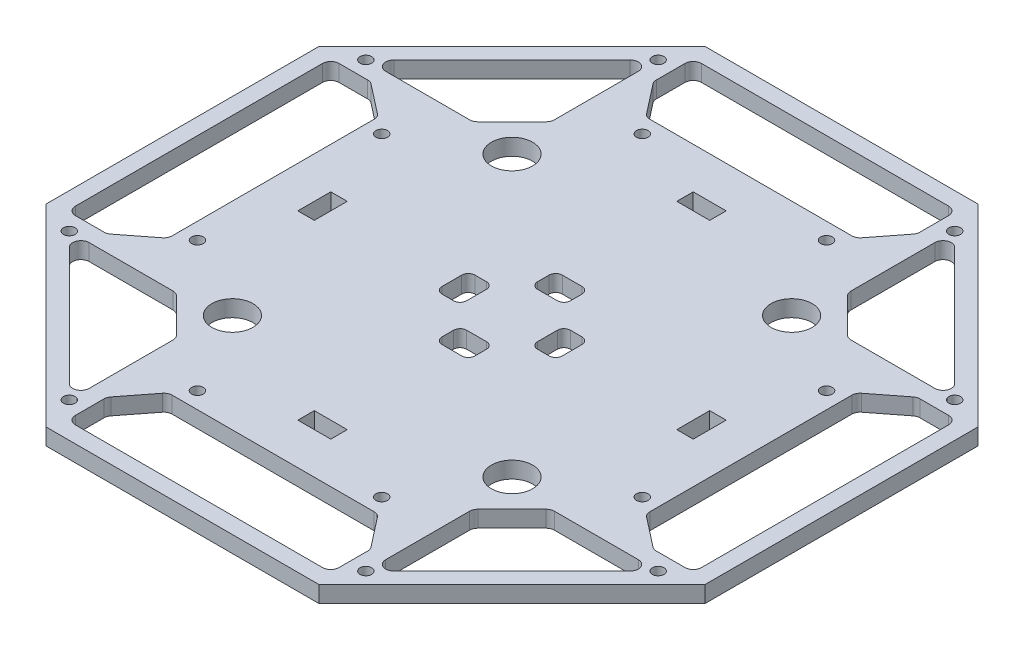
SolidWorks part; units mm, degrees
material "Custom Plastic"
ref_plane "Front Plane" through (0, 0, 0) normal (0, 0, 1) x (1, 0, 0)
ref_plane "Top Plane" through (0, 0, 0) normal (0, 1, 0) x (1, 0, 0)
ref_plane "Right Plane" through (0, 0, 0) normal (1, 0, 0) x (0, 0, -1)
ref_axis "Axis1" through (0, -0.2997, 0) along (0, 1, 0)
sketch "Base sketch" plane through (0, 0, 0) normal (0, 1, 0) x (1, 0, 0)
  line L1 (-127, 52.6051) -> (-127, -52.6051)
  line L2 (-127, -52.6051) -> (-52.6051, -127)
  line L3 (-52.6051, -127) -> (52.6051, -127)
  line L4 (52.6051, -127) -> (127, -52.6051)
  line L5 (127, -52.6051) -> (127, 52.6051)
  line L6 (127, 52.6051) -> (52.6051, 127)
  line L7 (52.6051, 127) -> (-52.6051, 127)
  line L8 (-52.6051, 127) -> (-127, 52.6051)
  circle A0 centre (0, 0) radius 127 construction
  dimension "D1" = 254
extrude "Base" add sketch "Base sketch" along normal blind 6.35
sketch "Sketch4" plane through (0, 6.35, 0) normal (0, 1, 0) x (1, 0, 0)
  line L0 (0, 0) -> (0, 127) construction
  line L1 (52.6051, 127) -> (-52.6051, 127) construction
  line L4 (-6.35, 69.85) -> (6.35, 69.85)
  line L5 (-6.35, 69.85) -> (-6.35, 76.2)
  line L6 (-6.35, 76.2) -> (6.35, 76.2)
  line L7 (6.35, 69.85) -> (6.35, 76.2)
  line L8 (-6.35, 69.85) -> (6.35, 76.2) construction
  line L10 (-6.35, 76.2) -> (6.35, 69.85) construction
  point P5 (0, 73.025)
  dimension "D1" = 6.35
  dimension "D2" = 12.7
  dimension "D3" = 53.975
extrude "Support cutouts" cut sketch "Sketch4" against normal up to next
pattern_circular "Support cutout pattern" count 4 over 360 about axis through (0, -0.2997, 0) along (0, 1, 0) of "Support cutouts"
sketch "Sketch11" plane through (0, 6.35, 0) normal (0, 1, 0) x (1, 0, 0)
  line L1 (98.425, 40.769) -> (40.769, 98.425) construction
  line L2 (40.769, 98.425) -> (-40.769, 98.425) construction
  line L3 (-40.769, 98.425) -> (-98.425, 40.769) construction
  line L4 (-98.425, 40.769) -> (-98.425, -40.769) construction
  line L5 (-98.425, -40.769) -> (-40.769, -98.425) construction
  line L6 (-40.769, -98.425) -> (40.769, -98.425) construction
  line L7 (40.769, -98.425) -> (98.425, -40.769) construction
  line L8 (98.425, -40.769) -> (98.425, 40.769) construction
  line L9 (-35.5085, 85.725) -> (-85.725, 35.5085)
  line L10 (-85.725, 35.5085) -> (-85.725, -35.5085)
  line L11 (-85.725, -35.5085) -> (-35.5085, -85.725)
  line L12 (-35.5085, -85.725) -> (35.5085, -85.725)
  line L13 (35.5085, -85.725) -> (85.725, -35.5085)
  line L14 (85.725, -35.5085) -> (85.725, 35.5085)
  line L15 (85.725, 35.5085) -> (35.5085, 85.725)
  line L16 (35.5085, 85.725) -> (-35.5085, 85.725)
  circle A0 centre (0, 0) radius 98.425 construction
  circle A1 centre (0, 0) radius 85.725 construction
  dimension "D1" = 196.85
  dimension "D2" = 12.7
hole_wizard "#8 Clearance Hole1" positions "Sketch13" profile "Sketch12" hole size "#8" standard "ANSI Inch" end condition through all
sketch "Sketch13" plane through (0, 6.35, 0) normal (0, 1, 0) x (1, 0, 0)
  point P0 (-85.725, 35.5085)
  point P3 (-35.5085, 85.725)
  point P6 (35.5085, 85.725)
  point P9 (85.725, 35.5085)
  point P12 (85.725, -35.5085)
  point P15 (35.5085, -85.725)
  point P18 (-35.5085, -85.725)
  point P21 (-85.725, -35.5085)
sketch "Sketch12" plane through (-85.725, 6.35, -35.5085) normal (1, 0, 0) x (0, 0, 1)
  line L0 (0, 0) -> (0, 6.35)
  line L1 (0, 6.35) -> (2.2479, 6.35)
  line L2 (2.2479, 6.35) -> (2.2479, 0)
  line L5 (2.2479, 0) -> (0, 0)
  line L11 (0, -6.35) -> (0, 107.95) construction
  dimension "Thru Hole Dia." = 4.4958
  dimension "Thru Hole Depth" = 6.35
sketch "Sketch14" plane through (0, 6.35, 0) normal (0, 1, 0) x (1, 0, 0)
  circle A0 centre (-53.8815, 53.8815) radius 7.9375
  circle A1 centre (53.8815, 53.8815) radius 7.9375
  circle A2 centre (53.8815, -53.8815) radius 7.9375
  circle A3 centre (-53.8815, -53.8815) radius 7.9375
  point P13 (0, 0)
  dimension "D2" = 15.875
  dimension "D1" = 76.2
  dimension "D3" = 4
extrude "Cable holes" cut sketch "Sketch14" against normal up to next
sketch "Sketch28" plane through (0, 6.35, 0) normal (0, 1, 0) x (1, 0, 0)
  line L0 (52.6051, 127) -> (-52.6051, 127) construction
  line L1 (57.15, 73.4808) -> (57.15, 105.8097)
  line L2 (62.5701, 108.0548) -> (108.0548, 62.5701)
  line L3 (71.2358, 58.0799) -> (58.0799, 71.2358)
  line L4 (-127, 52.6051) -> (-127, -52.6051) construction
  line L5 (105.8097, 57.15) -> (73.4808, 57.15)
  line L6 (73.4808, -57.15) -> (105.8097, -57.15)
  line L7 (108.0548, -62.5701) -> (62.5701, -108.0548)
  line L8 (58.0799, -71.2358) -> (71.2358, -58.0799)
  line L9 (57.15, -105.8097) -> (57.15, -73.4808)
  line L10 (-57.15, -73.4808) -> (-57.15, -105.8097)
  line L11 (-62.5701, -108.0548) -> (-108.0548, -62.5701)
  line L12 (-58.0799, 71.2358) -> (-71.2358, 58.0799)
  line L13 (-57.15, 105.8097) -> (-57.15, 73.4808)
  line L14 (-108.0548, 62.5701) -> (-62.5701, 108.0548)
  line L15 (-73.4808, 57.15) -> (-105.8097, 57.15)
  line L16 (-71.2358, -58.0799) -> (-58.0799, -71.2358)
  line L17 (-105.8097, -57.15) -> (-73.4808, -57.15)
  line L18 (-73.4808, 57.15) -> (-105.8097, 57.15) construction
  line L19 (-58.0799, 71.2358) -> (-71.2358, 58.0799) construction
  line L20 (0, 0) -> (-89.8026, 89.8026) construction
  line L21 (-52.6051, 127) -> (-127, 52.6051) construction
  arc A1 (62.5701, 108.0548) -> (57.15, 105.8097) centre (60.325, 105.8097) ccw
  arc A2 (57.15, 73.4808) -> (58.0799, 71.2358) centre (60.325, 73.4808) ccw
  arc A3 (71.2358, 58.0799) -> (73.4808, 57.15) centre (73.4808, 60.325) ccw
  circle A4 centre (-35.5085, 85.725) radius 2.2479 construction
  arc A5 (105.8097, 57.15) -> (108.0548, 62.5701) centre (105.8097, 60.325) ccw
  arc A6 (108.0548, -62.5701) -> (105.8097, -57.15) centre (105.8097, -60.325) ccw
  arc A7 (73.4808, -57.15) -> (71.2358, -58.0799) centre (73.4808, -60.325) ccw
  arc A8 (58.0799, -71.2358) -> (57.15, -73.4808) centre (60.325, -73.4808) ccw
  arc A9 (57.15, -105.8097) -> (62.5701, -108.0548) centre (60.325, -105.8097) ccw
  arc A10 (-62.5701, -108.0548) -> (-57.15, -105.8097) centre (-60.325, -105.8097) ccw
  arc A11 (-57.15, -73.4808) -> (-58.0799, -71.2358) centre (-60.325, -73.4808) ccw
  arc A12 (-73.4808, 57.15) -> (-71.2358, 58.0799) centre (-73.4808, 60.325) ccw
  arc A13 (-58.0799, 71.2358) -> (-57.15, 73.4808) centre (-60.325, 73.4808) ccw
  arc A14 (-57.15, 105.8097) -> (-62.5701, 108.0548) centre (-60.325, 105.8097) ccw
  arc A15 (-108.0548, 62.5701) -> (-105.8097, 57.15) centre (-105.8097, 60.325) ccw
  arc A16 (-71.2358, -58.0799) -> (-73.4808, -57.15) centre (-73.4808, -60.325) ccw
  arc A17 (-105.8097, -57.15) -> (-108.0548, -62.5701) centre (-105.8097, -60.325) ccw
  point P51 (0, 0)
  point P54 (-85.3124, 85.3124)
  point P55 (-64.6578, 64.6578)
  point P67 (0, 0)
  dimension "D3" = 3.175
  dimension "D1" = 6.35
  dimension "D5" = 4
extrude "lightenning 1" cut sketch "Sketch28" against normal through all
sketch "Sketch29" plane through (0, 6.35, 0) normal (0, 1, 0) x (1, 0, 0)
  line L0 (18.415, 0) -> (0, 0) construction
  line L1 (13.6525, -3.81) -> (13.6525, 3.81)
  line L2 (16.1925, -6.35) -> (20.6375, -6.35)
  line L3 (0, 18.415) -> (0, 0) construction
  line L4 (13.6525, -6.35) -> (23.1775, 6.35) construction
  line L5 (3.81, 13.6525) -> (-3.81, 13.6525)
  line L6 (6.35, 16.1925) -> (6.35, 20.6375)
  line L7 (3.81, 23.1775) -> (-3.81, 23.1775)
  line L8 (-6.35, 16.1925) -> (-6.35, 20.6375)
  line L9 (6.35, 13.6525) -> (-6.35, 23.1775) construction
  line L10 (6.35, 23.1775) -> (-6.35, 13.6525) construction
  line L11 (23.1775, -6.35) -> (13.6525, 6.35) construction
  line L12 (16.1925, 6.35) -> (20.6375, 6.35)
  line L13 (23.1775, -3.81) -> (23.1775, 3.81)
  line L14 (0, -18.415) -> (0, 0) construction
  line L15 (-3.81, -13.6525) -> (3.81, -13.6525)
  line L16 (-6.35, -16.1925) -> (-6.35, -20.6375)
  line L17 (-6.35, -13.6525) -> (6.35, -23.1775) construction
  line L18 (-6.35, -23.1775) -> (6.35, -13.6525) construction
  line L19 (6.35, -16.1925) -> (6.35, -20.6375)
  line L20 (-3.81, -23.1775) -> (3.81, -23.1775)
  line L21 (-18.415, 0) -> (0, 0) construction
  line L22 (-13.6525, 3.81) -> (-13.6525, -3.81)
  line L23 (-16.1925, 6.35) -> (-20.6375, 6.35)
  line L24 (-13.6525, 6.35) -> (-23.1775, -6.35) construction
  line L25 (-23.1775, 6.35) -> (-13.6525, -6.35) construction
  line L26 (-16.1925, -6.35) -> (-20.6375, -6.35)
  line L27 (-23.1775, 3.81) -> (-23.1775, -3.81)
  arc A0 (-3.81, 23.1775) -> (-6.35, 20.6375) centre (-3.81, 20.6375) ccw
  arc A1 (-3.81, 13.6525) -> (-6.35, 16.1925) centre (-3.81, 16.1925) cw
  arc A2 (3.81, 13.6525) -> (6.35, 16.1925) centre (3.81, 16.1925) ccw
  arc A3 (6.35, 20.6375) -> (3.81, 23.1775) centre (3.81, 20.6375) ccw
  arc A4 (13.6525, -3.81) -> (16.1925, -6.35) centre (16.1925, -3.81) ccw
  arc A5 (13.6525, 3.81) -> (16.1925, 6.35) centre (16.1925, 3.81) cw
  arc A6 (23.1775, 3.81) -> (20.6375, 6.35) centre (20.6375, 3.81) ccw
  arc A7 (20.6375, -6.35) -> (23.1775, -3.81) centre (20.6375, -3.81) ccw
  arc A8 (-3.81, -13.6525) -> (-6.35, -16.1925) centre (-3.81, -16.1925) ccw
  arc A9 (3.81, -13.6525) -> (6.35, -16.1925) centre (3.81, -16.1925) cw
  arc A10 (3.81, -23.1775) -> (6.35, -20.6375) centre (3.81, -20.6375) ccw
  arc A11 (-6.35, -20.6375) -> (-3.81, -23.1775) centre (-3.81, -20.6375) ccw
  arc A12 (-13.6525, 3.81) -> (-16.1925, 6.35) centre (-16.1925, 3.81) ccw
  arc A13 (-13.6525, -3.81) -> (-16.1925, -6.35) centre (-16.1925, -3.81) cw
  arc A14 (-23.1775, -3.81) -> (-20.6375, -6.35) centre (-20.6375, -3.81) ccw
  arc A15 (-20.6375, 6.35) -> (-23.1775, 3.81) centre (-20.6375, 3.81) ccw
  point P73 (0, 0)
  dimension "D4" = 2.54
  dimension "D1" = 18.415
  dimension "D2" = 9.525
  dimension "D3" = 12.7
extrude "Motor wire holes" cut sketch "Sketch29" against normal through all
sketch "Sketch30" plane through (0, 6.35, 0) normal (0, 1, 0) x (1, 0, 0)
  line L0 (57.15, 105.8097) -> (57.15, 73.4808) construction
  line L1 (108.0548, 62.5701) -> (62.5701, 108.0548) construction
  line L2 (-62.5701, 108.0548) -> (-108.0548, 62.5701) construction
  line L3 (-57.15, 73.4808) -> (-57.15, 105.8097) construction
  circle A0 centre (-57.15, 113.4749) radius 2.2479
  circle A1 centre (57.15, 113.4749) radius 2.2479
  circle A2 centre (35.5085, 85.725) radius 2.2479 construction
extrude "next stage holes" cut sketch "Sketch30" against normal through all
pattern_circular "CirPattern1" count 4 every 90 about axis through (0, -0.2997, 0) along (0, 1, 0) of "next stage holes"
sketch "Sketch31" plane through (0, 6.35, 0) normal (0, 1, 0) x (1, 0, 0)
  line L0 (-120.65, 47.625) -> (-120.65, -47.625)
  line L1 (-113.4749, -57.15) -> (-85.725, -35.5085) construction
  line L2 (-92.075, 0) -> (-92.075, -38.9104)
  line L4 (-127, 0) -> (-120.65, 0) construction
  line L5 (-127, 52.6051) -> (-127, -52.6051) construction
  line L6 (-120.65, 0) -> (0, 0) construction
  line L7 (-113.4749, 57.15) -> (-85.725, 35.5085) construction
  line L9 (-106.4243, -50.8) -> (-117.475, -50.8)
  line L10 (-93.2975, -41.4141) -> (-104.4717, -50.1286)
  line L14 (0, 127) -> (0, 120.65) construction
  line L26 (0, -127) -> (0, -120.65) construction
  line L27 (-92.075, 0) -> (-92.075, 38.9104)
  line L28 (-93.2975, 41.4141) -> (-104.4717, 50.1286)
  line L29 (-106.4243, 50.8) -> (-117.475, 50.8)
  line L31 (49.4733, 120.65) -> (-49.4733, 120.65) [skipped]
  line L33 (120.65, -49.4733) -> (120.65, 49.4733) [skipped]
  line L35 (-49.4733, -120.65) -> (49.4733, -120.65) [skipped]
  line L37 (120.65, 0) -> (0, 0) construction
  line L38 (127, 0) -> (120.65, 0) construction
  line L39 (0, 120.65) -> (0, 0) construction
  line L40 (0, -120.65) -> (0, 0) construction
  arc A0 (-120.65, 47.625) -> (-117.475, 50.8) centre (-117.475, 47.625) cw
  arc A1 (-104.4717, 50.1286) -> (-106.4243, 50.8) centre (-106.4243, 47.625) ccw
  arc A3 (-92.075, 38.9104) -> (-93.2975, 41.4141) centre (-95.25, 38.9104) ccw
  arc A5 (-92.075, -38.9104) -> (-93.2975, -41.4141) centre (-95.25, -38.9104) cw
  arc A7 (-104.4717, -50.1286) -> (-106.4243, -50.8) centre (-106.4243, -47.625) cw
  arc A8 (-120.65, -47.625) -> (-117.475, -50.8) centre (-117.475, -47.625) ccw
  arc A17 (-108.0548, 62.5701) -> (-105.8097, 57.15) centre (-105.8097, 60.325) ccw construction
  point P0 (-92.075, -40.4607)
  point P23 (-105.3326, 50.8)
  point P28 (-92.075, 40.4607)
  point P48 (-82.55, 0)
  point P49 (-105.3326, -50.8)
  point P73 (0, 0)
  dimension "D4" = 4
  dimension "D1" = 6.35
  dimension "D2" = 6.35
  dimension "D5" = 6.35
extrude "lightenning 2" cut sketch "Sketch31" against normal through all
pattern_circular "CirPattern2" count 4 every 90 about axis through (0, -0.2997, 0) along (0, 1, 0) of "lightenning 2"
equation "\"MAT_THICKNESS\"=0.25"
equation "\"D1@Base\"=\"MAT_THICKNESS\""
equation "\"D1@Sketch4\"=\"MAT_THICKNESS\""
